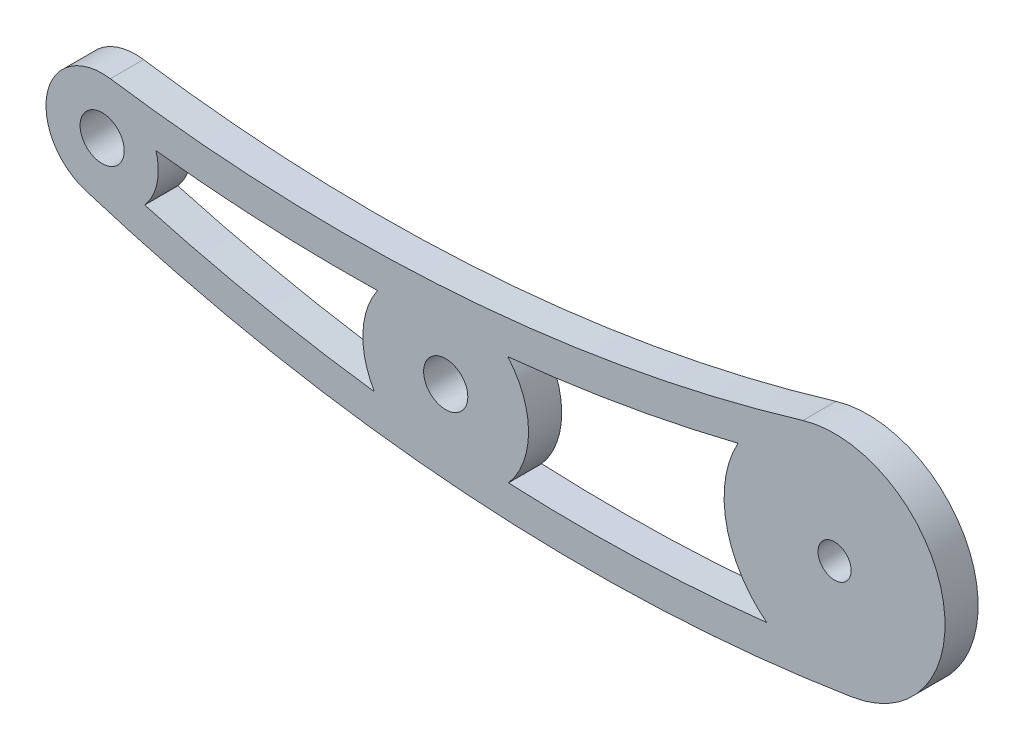
SolidWorks part; units mm, degrees
material "1060 Alloy"
ref_plane "Front Plane" through (0, 0, 0) normal (0, 0, 1) x (1, 0, 0)
ref_plane "Top Plane" through (0, 0, 0) normal (0, 1, 0) x (1, 0, 0)
ref_plane "Right Plane" through (0, 0, 0) normal (1, 0, 0) x (0, 0, -1)
sketch "Sketch1" plane through (0, 0, 0) normal (0, 0, 1) x (1, 0, 0)
  line L0 (0, 0) -> (66.3, 0)
  line L1 (0, -8) -> (66.3, -8)
  line L2 (0, 8) -> (66.3, 8)
  line L3 (0, -5) -> (66.3, -5)
  circle A0 centre (66.3, 0) radius 1.5
  circle A1 centre (0, 0) radius 2
  arc A2 (0, -8) -> (0, 8) centre (0, 0) cw
  arc A3 (66.3, -8) -> (66.3, 8) centre (66.3, 0) ccw
  circle A4 centre (31.1, -3.74) radius 2
  circle A5 centre (33.15, 176.6537) radius 184.6537
  circle A6 centre (33.15, 176.6537) radius 174.6537
  circle A7 centre (0, 0) radius 5.0835
  circle A8 centre (66.3, 0) radius 5.0835
  dimension "D2" = 3
  dimension "D1" = 4
extrude "Extrude1" add sketch "Sketch1" along normal blind 3 contours A7 A5 L3 A1 | A8 L0 A7 L3 A4 | A8 A6 A7 L0 | A8 L3 A5 A0 | A8 L3 A4 A7 A5 | A5 A7 L3 | L3 A8 A5 region at (3.7955, -3.1624, 0) region at (33.15, 1.5509, 0) region at (33.2303, -2.5109, 0) region at (62.4982, 3.1548, 0) region at (0.4491, -5.0241, 0) region at (33.175, -6.2124, 0) region at (65.8509, -5.0241, 0)
sketch "Sketch2" plane through (0, 0, 3) normal (0, 0, 1) x (1, 0, 0)
  circle A0 centre (31.1, -3.74) radius 7.5 construction
  arc A1 (67.8926, -9.8724) -> (63.4272, 9.5785) centre (66.3, 0) ccw
  arc A2 (0.742, 5.029) -> (63.4272, 9.5785) centre (21.8615, 148.164) ccw
  arc A3 (0.9376, 4.9963) -> (-2.1931, -4.5861) centre (0, 0) ccw construction
  arc A4 (67.8926, -9.8724) -> (-1.5236, -4.8498) centre (43.8061, 139.438) cw
  arc A6 (0.742, 5.029) -> (-1.5236, -4.8498) centre (0, 0) ccw
  arc M1 (-2.1931, -4.5861) -> (68.4931, -4.5861) centre (33.15, 176.6537) ccw
  arc M2 (68.4931, -4.5861) -> (65.3624, 4.9963) centre (66.3, 0) ccw
  arc M3 (65.3624, 4.9963) -> (0.9376, 4.9963) centre (33.15, 176.6537) cw
  arc M4 (0.9376, 4.9963) -> (-2.1931, -4.5861) centre (0, 0) ccw
  circle M5 centre (31.1, -3.74) radius 2
  circle M6 centre (0, 0) radius 2
  circle M7 centre (66.3, 0) radius 1.5
  dimension "D1" = 15
  dimension "D2" = 20
extrude "Boss-Extrude1" add sketch "Sketch2" against normal blind 3 contours M4 M1 M2 M3 M5 M7 M6 | A6 A4 A1 A2 M1 M4 M3 M2 region at (32.9504, -10.5958, 3) region at (33.4408, -1.7674, 3)
sketch "Sketch3" plane through (0, 0, 3) normal (0, 0, 1) x (1, 0, 0)
  arc A4 (3.8522, -3.317) -> (4.8693, 1.4601) centre (0, 0) ccw
  arc A5 (24.9211, 0.511) -> (24.6452, -7.5591) centre (31.1, -3.74) ccw
  arc A6 (57.5597, 4.8587) -> (60.1654, -7.8972) centre (66.3, 0) ccw
  arc A7 (36.7182, 1.2285) -> (57.5597, 4.8587) centre (21.8615, 148.164) ccw
  arc A8 (0.3041, 2.0612) -> (-0.6245, -1.9877) centre (0, 0) ccw
  arc A9 (-0.6245, -1.9877) -> (67.4148, -6.9107) centre (43.8061, 139.438) ccw
  arc A10 (67.4148, -6.9107) -> (64.289, 6.7049) centre (66.3, 0) ccw
  arc A11 (0.3041, 2.0612) -> (64.289, 6.7049) centre (21.8615, 148.164) ccw
  arc A12 (0.3041, 2.0612) -> (-0.6245, -1.9877) centre (0, 0) ccw
  arc A13 (3.8522, -3.317) -> (24.6452, -7.5591) centre (43.8061, 139.438) ccw
  arc A15 (4.8693, 1.4601) -> (24.9211, 0.511) centre (21.8615, 148.164) ccw
  arc A16 (36.7813, -8.6361) -> (60.1654, -7.8972) centre (43.8061, 139.438) ccw
  arc A17 (36.7813, -8.6361) -> (36.7182, 1.2285) centre (31.1, -3.74) ccw
  dimension "D1" = 3
extrude "Cut-Extrude1" cut sketch "Sketch3" against normal blind 5 contours A15 A4 A13 A5 | A17 A16 A6 A7 region at (15.0924, -2.5798, 3) region at (48.0374, -3.0102, 3)
move or copy body "Body-Move/Copy1" [suppressed] bodies to move or copy 105
move or copy body "Body-Move/Copy2" [suppressed] bodies to move or copy 105
